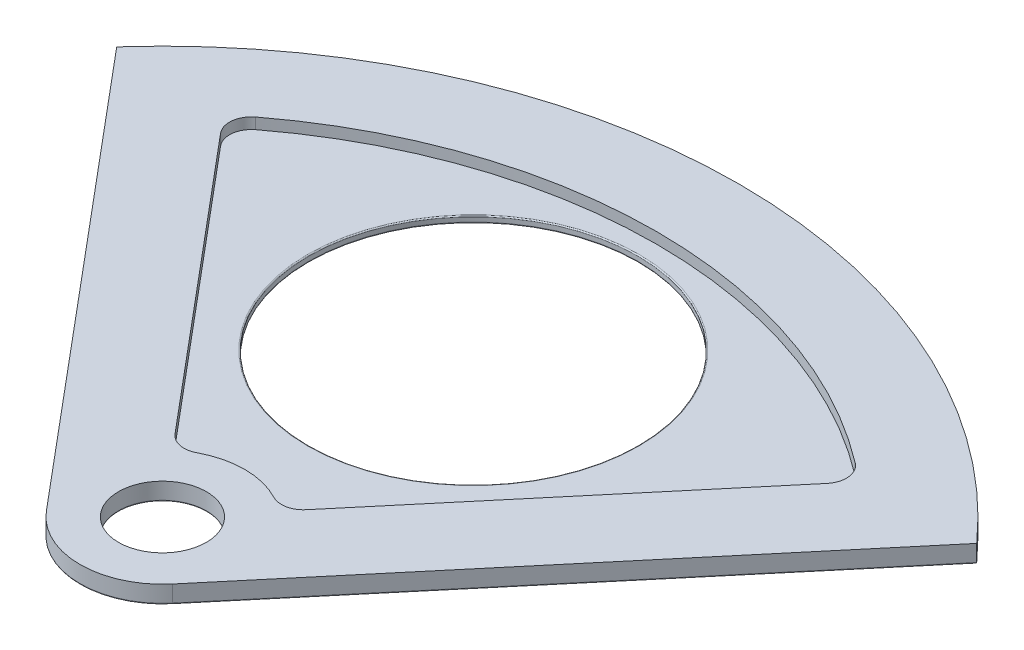
SolidWorks part; units mm, degrees
ref_plane "Front Plane" through (0, 0, 0) normal (0, 0, 1) x (1, 0, 0)
ref_plane "Top Plane" through (0, 0, 0) normal (0, 1, 0) x (1, 0, 0)
ref_plane "Right Plane" through (0, 0, 0) normal (1, 0, 0) x (0, 0, -1)
sketch "Sketch1" plane through (0, 0, 0) normal (0, 1, 0) x (1, 0, 0)
  line L0 (-12.2451, 14.5931) -> (-73.4706, 87.5589)
  line L1 (12.2451, 14.5931) -> (73.4706, 87.5589)
  line L2 (0, 0) -> (0, 231.0417) construction
  line L3 (-14.5931, -12.2451) -> (-99.4297, 88.8592)
  line L4 (14.5931, -12.2451) -> (99.4297, 88.8592)
  arc A0 (73.4706, 87.5589) -> (-73.4706, 87.5589) centre (0, 0) ccw
  arc A1 (12.2451, 14.5931) -> (-12.2451, 14.5931) centre (0, 0) ccw
  circle A2 centre (0, 0) radius 10.16
  arc A3 (-14.5931, -12.2451) -> (14.5931, -12.2451) centre (0, 0) ccw
  arc A4 (-99.4297, 88.8592) -> (99.4297, 88.8592) centre (0, 0) cw
  dimension "D1" = 228.6
  dimension "D2" = 38.1
  dimension "D3" = 80
  dimension "D4" = 20.32
  dimension "D5" = 19.05
  dimension "D6" = 19.05
extrude "Boss-Extrude1" add sketch "Sketch1" along normal blind 2.54
fillet "Fillet1" radius 5.08 4 edges at (12.2451, 1.27, -14.5931) (-12.2451, 1.27, -14.5931) (-73.4706, 1.27, -87.5589) (73.4706, 1.27, -87.5589)
sketch "Sketch2" plane through (0, 0, 0) normal (0, -1, 0) x (1, 0, 0)
  line L2 (-14.5931, 12.2451) -> (-99.4297, -88.8592)
  line L3 (99.4297, -88.8592) -> (14.5931, 12.2451)
  line L4 (-14.5931, 12.2451) -> (-99.4297, -88.8592)
  line L5 (99.4297, -88.8592) -> (14.5931, 12.2451)
  circle A0 centre (0, 0) radius 10.16 construction
  circle A1 centre (0, 0) radius 10.16
  arc A2 (14.5931, 12.2451) -> (-14.5931, 12.2451) centre (0, 0) ccw
  arc A3 (-99.4297, -88.8592) -> (99.4297, -88.8592) centre (0, 0) ccw
  arc A4 (14.5931, 12.2451) -> (-14.5931, 12.2451) centre (0, 0) ccw
  arc A5 (-99.4297, -88.8592) -> (99.4297, -88.8592) centre (0, 0) ccw
  circle A6 centre (0, -71.892) radius 38.1
  dimension "D2" = 76.2
  dimension "D3" = 71.892
  dimension "D1" = 0
extrude "Boss-Extrude2" add sketch "Sketch2" along normal blind 1.524
fillet "Fillet2" radius 0.254 7 edges at (38.1, -1.524, -71.892) (57.0114, -1.524, -38.307) (0, -1.524, -133.35) (-57.0114, -1.524, -38.307) (0, -1.524, 19.05) (10.16, -1.524, 0) (38.1, 0, -71.892)
sketch "Sketch3" plane through (0, -1.524, 0) normal (0, -1, 0) x (1, 0, 0)
  circle A0 centre (0, -71.892) radius 38.1
  dimension "D1" = 76.2
